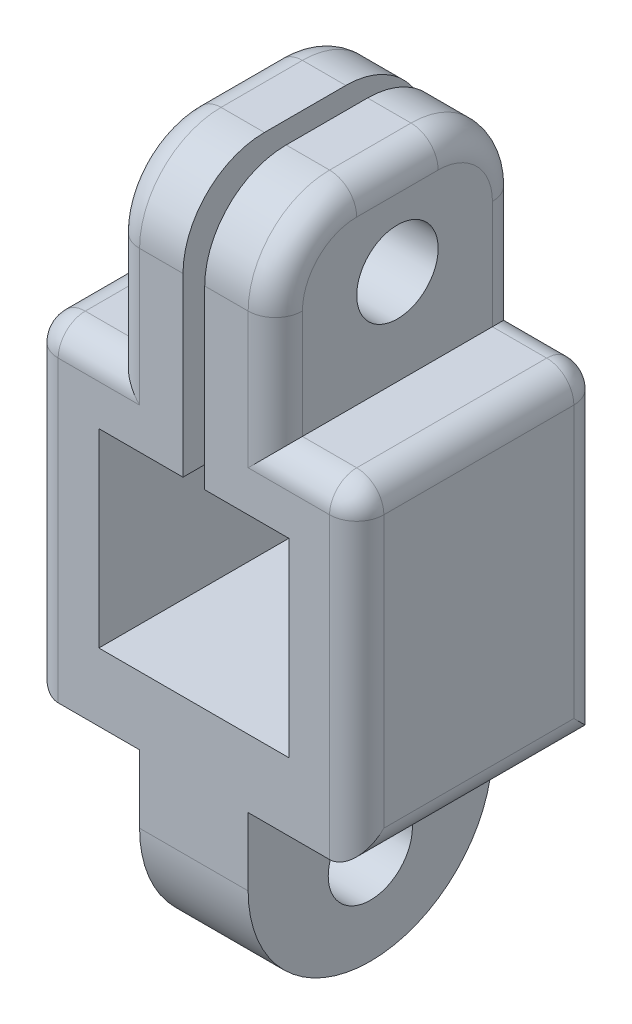
SolidWorks part; units mm, degrees
ref_plane "前视基准面" through (0, 0, 0) normal (0, 0, 1) x (1, 0, 0)
ref_plane "上视基准面" through (0, 0, 0) normal (0, 1, 0) x (1, 0, 0)
ref_plane "右视基准面" through (0, 0, 0) normal (1, 0, 0) x (0, 0, -1)
sketch "草图1" plane through (0, 0, 0) normal (0, 0, 1) x (1, 0, 0)
  line L0 (-1.5, -6) -> (-1.5, -13)
  line L1 (-3.5, 3.5) -> (3.5, 3.5)
  line L2 (-3.5, 3.5) -> (-3.5, -3.5)
  line L3 (-3.5, -3.5) -> (3.5, -3.5)
  line L4 (3.5, 3.5) -> (3.5, -3.5)
  line L5 (-3.5, 3.5) -> (3.5, -3.5) construction
  line L6 (-3.5, -3.5) -> (3.5, 3.5) construction
  line L7 (-6, 6) -> (6, 6)
  line L8 (-6, 6) -> (-6, -6)
  line L9 (-6, -6) -> (6, -6)
  line L10 (6, 6) -> (6, -6)
  line L11 (-6, 6) -> (6, -6) construction
  line L12 (-6, -6) -> (6, 6) construction
  line L13 (-1.5, -13) -> (3.5, -13)
  line L14 (3.5, -13) -> (3.5, -6)
  line L15 (0, 0) -> (0, 9.9638) construction
  line L17 (0, 6) -> (3, 6)
  line L18 (0, 6) -> (0, 13)
  line L19 (0, 13) -> (3, 13)
  line L20 (3, 6) -> (3, 13)
  line L21 (0, 6) -> (-3, 6)
  line L22 (0, 6) -> (0, 13)
  line L23 (0, 13) -> (-3, 13)
  line L24 (-3, 6) -> (-3, 13)
  point P0 (0, 0)
  point P6 (0, 0)
  dimension "D1" = 7
  dimension "D2" = 7
  dimension "D3" = 12
  dimension "D4" = 12
  dimension "D5" = 2
  dimension "D6" = 7
  dimension "D7" = 5
  dimension "D8" = 7
  dimension "D9" = 3
  dimension "D10" = 3
  dimension "D11" = 7
extrude "凸台-拉伸1" add sketch "草图1" along normal blind 9 contours L24 L7 L18 L23 | L7 L20 L19 L18 | L10 L7 L8 L9 L1 L4 L3 L2 | L13 L14 L9 L0 region at (1, -9.5, 0) region at (-3.75, -5.8303, 0) region at (-1.5, 9.5, 0) region at (1.5, 9.5, 0)
sketch "草图2" plane through (0, 0, 9) normal (0, 0, 1) x (1, 0, 0)
  line L0 (0, 16.6392) -> (0, -1.0512) construction
  line L1 (3, 13) -> (-3, 13) construction
  line L2 (0, 13) -> (0.4, 13)
  line L4 (0, 3.5) -> (0.4, 3.5)
  line L5 (0.4, 13) -> (0.4, 3.5)
  line L6 (-3.5, 3.5) -> (3.5, 3.5) construction
  line L8 (0, 13) -> (-0.4, 13)
  line L10 (0, 3.5) -> (-0.4, 3.5)
  line L11 (-0.4, 13) -> (-0.4, 3.5)
  dimension "D1" = 0.4
  dimension "D2" = 0.4
extrude "切除-拉伸1" cut sketch "草图2" against normal through all contours L2 L5 L4 L10 L11 L8
fillet "圆角2" radius 3 4 edges at (1.7, 13, 0) (-1.7, 13, 0) (-1.7, 13, 9) (1.7, 13, 9)
sketch "草图4" plane through (3, 0, 0) normal (1, 0, 0) x (0, 0, -1)
  line L0 (-4.5, 6) -> (-4.5, 9.5) construction
  line L1 (-9, 6) -> (0, 6) construction
  circle A0 centre (-4.5, 9.5) radius 1.5
  dimension "D2" = 3
  dimension "D1" = 3.5
extrude "切除-拉伸3" cut sketch "草图4" against normal through all
fillet "圆角3" radius 1 11 edges at (3, 8, 0) (3, 12.1213, 0.8787) (3, 13, 4.5) (3, 12.1213, 8.1213) (3, 8, 9) (6, -6, 4.5) (6, 0, 0) (6, 0, 9) (6, 6, 4.5) (4.5, 6, 0) (4.5, 6, 9)
fillet "圆角4" radius 1 10 edges at (-3, 8, 0) (-3, 12.1213, 0.8787) (-3, 13, 4.5) (-3, 12.1213, 8.1213) (-3, 8, 9) (-6, -6, 4.5) (-6, 0, 0) (-4.5, 6, 0) (-4.5, 6, 9) (-6, 0, 9)
fillet "圆角5" radius 1 3 edges at (-5.7071, 5.7071, 8.7071) (-5.7071, 5.7071, 0.2929) (-6, 6, 4.5)
sketch "草图5" plane through (0, 0, 9) normal (0, 0, 1) x (1, 0, 0)
  line L1 (-1.5, -6) -> (3.5, -6)
  line L2 (-1.5, -6) -> (-1.5, -13)
  line L3 (-1.5, -13) -> (3.5, -13)
  line L4 (3.5, -6) -> (3.5, -13)
extrude "切除-拉伸4" cut sketch "草图5" against normal blind 9
sketch "草图6" plane through (0, -6, 0) normal (0, -1, 0) x (1, 0, 0)
  line L0 (0, 10.5627) -> (0, -2.0403) construction
  line L1 (-5, 9) -> (5, 9) construction
  line L2 (0, 9) -> (-2, 9)
  line L4 (0, 0) -> (-2, 0)
  line L5 (-2, 9) -> (-2, 0)
  line L6 (-5, 0) -> (5, 0) construction
  line L8 (0, 9) -> (2, 9)
  line L10 (0, 0) -> (2, 0)
  line L11 (2, 9) -> (2, 0)
  dimension "D1" = 2
  dimension "D2" = 2
extrude "凸台-拉伸2" add sketch "草图6" along normal blind 7
fillet "圆角6" radius 4.5 2 edges at (0, -13, 0) (0, -13, 9)
sketch "草图7" plane through (-2, 0, 0) normal (-1, 0, 0) x (0, 0, 1)
  line L0 (4.5, -13) -> (4.5, -9.5) construction
  circle A0 centre (4.5, -9.5) radius 1.55
  dimension "D2" = 3.1
  dimension "D1" = 3.5
extrude "切除-拉伸5" cut sketch "草图7" against normal blind 4
